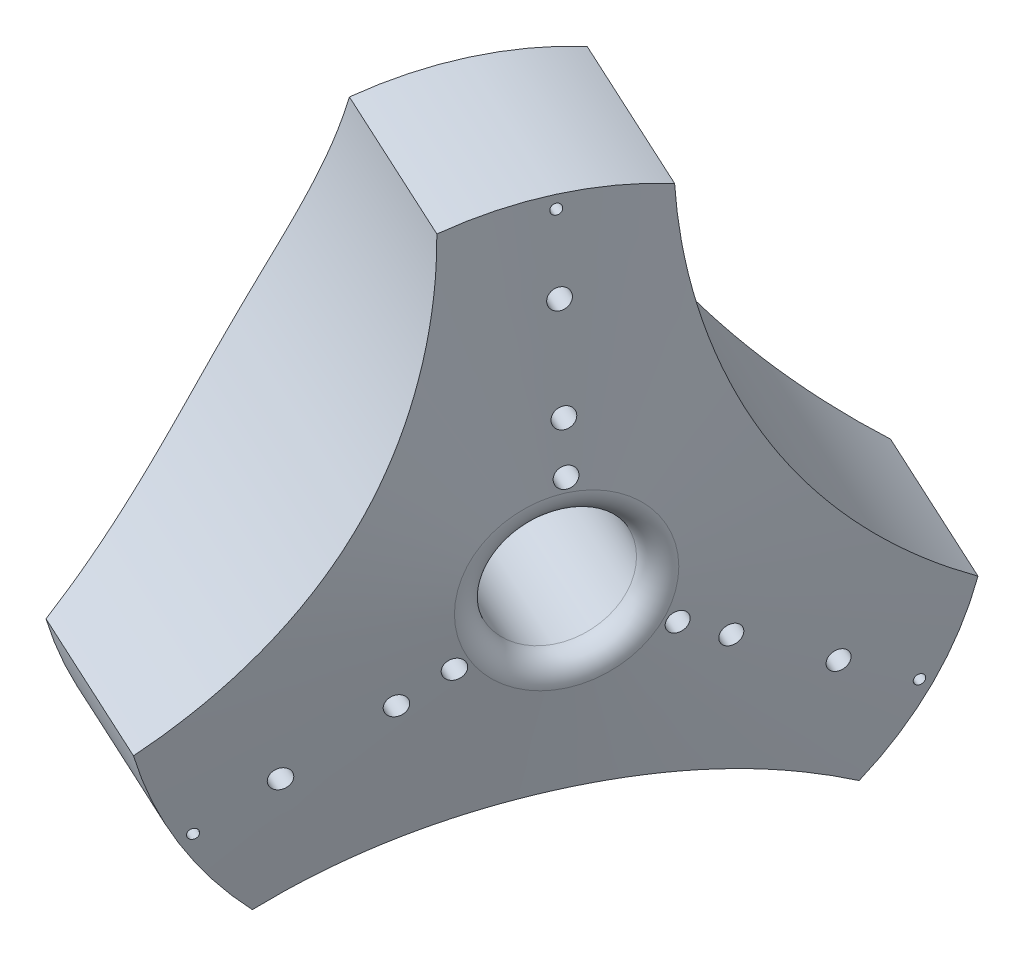
SolidWorks part; units mm, degrees
material "ABS"
ref_plane "前视基准面" through (0, 0, 0) normal (0, 0, 1) x (1, 0, 0)
ref_plane "上视基准面" through (0, 0, 0) normal (0, 1, 0) x (1, 0, 0)
ref_plane "右视基准面" through (0, 0, 0) normal (1, 0, 0) x (0, 0, -1)
other "Configuration Table"
sketch "草图1" plane through (0, 0, 0) normal (0, 1, 0) x (1, 0, 0)
  line L0 (0, 0) -> (50000, 0) construction
  line L1 (0, 0) -> (43301.2702, 25000) construction
  line L2 (0, 0) -> (24999.9996, 43301.2704) construction
  line L3 (0, 0) -> (0, 50000) construction
  line L4 (0, 0) -> (-25000, 43301.2702) construction
  line L5 (0, 0) -> (-43301.2704, 24999.9996) construction
  line L10 (33.4412, 57.9218) -> (0, 73.354)
  line L11 (0, 73.354) -> (0, 147.7852)
  line L12 (0, 147.7852) -> (67.3734, 116.6941)
  line L13 (18.3541, 0) -> (55.6014, 0)
  line L14 (-293.1662, 0) -> (-96.7748, 0)
  line L15 (67.3734, 116.6941) -> (33.4412, 57.9218)
  line L16 (36.9778, 130.7209) -> (32.7877, 121.641) construction
  line L17 (32.7877, 121.641) -> (62.3525, 107.9976)
  line L18 (32.7877, 121.641) -> (0, 136.7717)
  spline S0 degree 4 poles (0, -13.9122) (0.4288, -13.9878) (1.2926, -14.1039) (2.6002, -14.1722) (4.3419, -14.0551) (6.0103, -13.7444) (7.773, -13.21) (9.593, -12.4079) (11.2813, -11.3833) (13.0108, -9.9981) (14.579, -8.3636) (15.8921, -6.573) (16.7894, -4.9125) (17.3145, -3.6768) (17.5885, -2.9241) (17.7037, -2.5872) (17.8123, -2.2481) (17.9142, -1.9072) (18.0095, -1.5637) (18.0983, -1.2182) (18.1691, -0.9197) (18.2269, -0.6559) (18.2831, -0.3813) (18.3354, -0.109) (18.3711, 0.0925) (18.4139, 0.3573) (18.4465, 0.5746) (18.4705, 0.7447) (18.4976, 0.9523) (18.5267, 1.1986) (18.5568, 1.4891) (18.5855, 1.8227) (18.6082, 2.1561) (18.625, 2.4897) (18.6415, 2.9908) (18.6444, 3.7428) (18.6, 4.7901) (18.4544, 6.1268) (18.1183, 7.9493) (17.5241, 9.9881) (16.6153, 12.1533) (15.4328, 14.2054) (14.026, 16.1623) (12.2754, 18.1012) (10.149, 19.9482) (7.4457, 21.6944) (4.4784, 23.0742) (1.2971, 24.0486) (-2.1866, 24.6091) (-5.9175, 24.6633) (-9.7618, 24.1432) (-13.6227, 23.0043) (-17.2722, 21.3076) (-20.6387, 19.103) (-24.4169, 15.784) (-28.1648, 11.0227) (-31.3154, 4.4225) (-32.9538, -4.4321) (-32.0375, -14.0948) (-28.1424, -23.7302) (-21.3685, -32.1908) (-12.5515, -38.4704) (-2.4126, -42.2287) (8.3331, -43.3372) (19.0234, -41.8455) (29.7828, -37.6697) (40.3424, -30.2375) (49.4452, -19.1893) (55.5551, -4.7492) (57.3753, 11.4017) (54.7581, 27.4228) (48.0949, 42.2071) (37.9905, 54.8719) (25.1812, 64.7711) (10.4646, 71.4886) (-5.3559, 74.8179) (-21.5135, 74.7355) (-37.3086, 71.3698) (-52.1281, 64.9701) (-65.4574, 55.8769) (-76.8843, 44.4931) (-86.0992, 31.2617) (-92.9569, 16.4959) (-98.2612, -3.1071) (-99.3529, -27.5578) (-93.1302, -55.5464) (-77.0987, -83.8533) (-53.8578, -106.5556) (-25.4602, -122.2617) (5.9606, -130.2467) (38.3519, -130.3634) (69.8553, -122.9377) (98.8778, -108.6588) (124.1284, -88.4759) (144.6286, -63.5047) (159.7045, -34.9474) (168.9656, -4.026) (172.2746, 28.0696) (169.7138, 60.222) (161.5485, 91.4149) (148.1919, 120.752) (130.171, 147.4681) (108.095, 170.9338) (82.6276, 190.6548) (54.4619, 206.2675) (24.299, 217.5313) (-7.1689, 224.319) (-39.2739, 226.6058) (-71.3835, 224.4579) (-98.969, 218.8252) (-121.9134, 211.4493) (-140.4165, 203.6877) (-154.7919, 196.546) (-168.6874, 188.5108) (-182.0538, 179.6235) (-196.4446, 168.7156) (-208.5171, 158.129) (-219.9251, 146.8372) (-231.9749, 133.3951) (-241.9655, 120.8263) (-251.0758, 107.6061) (-258.3626, 95.6046) (-263.2354, 86.8412) (-266.9323, 79.7223) (-270.4259, 72.5015) (-273.7143, 65.185) (-276.4108, 58.7049) (-278.5921, 53.0984) (-280.3227, 48.3937) (-281.6549, 44.6108) (-282.9345, 40.8105) (-284.1616, 36.9917) (-285.3356, 33.1583) (-286.4574, 29.3057) (-287.5253, 25.4437) (-288.5419, 21.5581) (-289.5026, 17.675) (-290.3013, 14.2402) (-290.9454, 11.3302) (-291.4717, 8.8337) (-291.8579, 6.9561) (-292.2757, 4.8213) (-292.5987, 3.1456) (-293.0036, 0.9209) (-293.2168, -0.28) (-293.5445, -2.179) (-293.8363, -3.9367) (-294.1828, -6.1075) (-294.5484, -8.5333) (-294.8987, -10.9902) (-295.2261, -13.4346) (-295.5347, -15.89) (-295.8945, -18.9572) (-296.2863, -22.6451) (-296.6843, -26.9519) (-297.0589, -31.8818) (-297.3529, -36.8165) (-297.5669, -41.7558) (-297.7007, -46.6976) (-297.7547, -51.6411) (-297.729, -56.5848) (-297.624, -61.5274) (-297.4397, -66.4677) (-296.9135, -76.3411) (-295.6855, -89.8862) (-293.2164, -107.0261) (-288.82, -127.5848) (-284.8275, -141.8776) (-281.7816, -151.2859) (-280.1641, -155.9573) knots 0 0 0 0 0 0.000986 0.001973 0.002959 0.003945 0.004822 0.006138 0.007453 0.008403 0.009829 0.011255 0.012465 0.012667 0.012868 0.01307 0.013272 0.013473 0.013675 0.013876 0.014078 0.014179 0.01428 0.014481 0.01467 0.014765 0.01486 0.014954 0.015049 0.015238 0.015427 0.015617 0.015806 0.015995 0.016184 0.016752 0.017509 0.018368 0.019228 0.020946 0.022309 0.023673 0.024581 0.026398 0.028215 0.030031 0.031848 0.033788 0.035728 0.037999 0.04027 0.042541 0.044813 0.047084 0.049355 0.053897 0.05844 0.063467 0.069524 0.07558 0.081637 0.087693 0.093749 0.099806 0.105862 0.111919 0.119671 0.128756 0.137841 0.146925 0.15601 0.165095 0.174179 0.183264 0.192349 0.201434 0.210519 0.219603 0.228688 0.237773 0.246858 0.255942 0.265027 0.274475 0.292645 0.310814 0.328984 0.347153 0.365322 0.383492 0.401661 0.41983 0.438 0.456169 0.474339 0.492508 0.510678 0.528847 0.547017 0.565186 0.583356 0.601525 0.619695 0.637864 0.656034 0.674203 0.692373 0.710542 0.728712 0.746881 0.755966 0.765051 0.774136 0.78322 0.792305 0.80139 0.815017 0.81956 0.828644 0.842271 0.851356 0.855899 0.860441 0.864984 0.869526 0.874068 0.878611 0.880882 0.883153 0.885424 0.887695 0.889967 0.892238 0.894509 0.89678 0.899052 0.901323 0.903594 0.90473 0.905865 0.907001 0.908137 0.909272 0.910408 0.911108 0.911808 0.913208 0.914607 0.916007 0.917407 0.918807 0.920207 0.921607 0.924407 0.927206 0.930006 0.932806 0.935606 0.938405 0.941205 0.944005 0.946805 0.949604 0.952404 0.966403 0.977602 0.988801 1 1 1 1 1 construction
  spline S1 degree 4 poles (18.3541, 0) (18.3671, 0.0737) (18.3859, 0.1846) (18.4139, 0.3573) (18.4465, 0.5746) (18.4705, 0.7447) (18.4976, 0.9523) (18.5267, 1.1986) (18.5568, 1.4891) (18.5855, 1.8227) (18.6082, 2.1561) (18.625, 2.4897) (18.6415, 2.9908) (18.6444, 3.7428) (18.6, 4.7901) (18.4544, 6.1268) (18.1183, 7.9493) (17.5241, 9.9881) (16.6153, 12.1533) (15.4328, 14.2054) (14.026, 16.1623) (12.2754, 18.1012) (10.149, 19.9482) (7.4457, 21.6944) (4.4784, 23.0742) (1.2971, 24.0486) (-2.1866, 24.6091) (-5.9175, 24.6633) (-9.7618, 24.1432) (-13.6227, 23.0043) (-17.2722, 21.3076) (-20.6387, 19.103) (-24.4169, 15.784) (-28.1648, 11.0227) (-31.3154, 4.4225) (-32.9538, -4.4321) (-32.0375, -14.0948) (-28.1424, -23.7302) (-21.3685, -32.1908) (-12.5515, -38.4704) (-2.4126, -42.2287) (8.3331, -43.3372) (19.0234, -41.8455) (29.7828, -37.6697) (40.3424, -30.2375) (49.4452, -19.1893) (55.5551, -4.7492) (57.3753, 11.4017) (54.7581, 27.4228) (48.0949, 42.2071) (37.9905, 54.8719) (25.1812, 64.7711) (10.4646, 71.4886) (-5.3559, 74.8179) (-21.5135, 74.7355) (-37.3086, 71.3698) (-52.1281, 64.9701) (-65.4574, 55.8769) (-76.8843, 44.4931) (-86.0992, 31.2617) (-92.9569, 16.4959) (-98.2612, -3.1071) (-99.3529, -27.5578) (-93.1302, -55.5464) (-77.0987, -83.8533) (-53.8578, -106.5556) (-25.4602, -122.2617) (5.9606, -130.2467) (38.3519, -130.3634) (69.8553, -122.9377) (98.8778, -108.6588) (124.1284, -88.4759) (144.6286, -63.5047) (159.7045, -34.9474) (168.9656, -4.026) (172.2746, 28.0696) (169.7138, 60.222) (161.5485, 91.4149) (148.1919, 120.752) (130.171, 147.4681) (108.095, 170.9338) (82.6276, 190.6548) (54.4619, 206.2675) (24.299, 217.5313) (-7.1689, 224.319) (-39.2739, 226.6058) (-71.3835, 224.4579) (-98.969, 218.8252) (-121.9134, 211.4493) (-140.4165, 203.6877) (-154.7919, 196.546) (-168.6874, 188.5108) (-182.0538, 179.6235) (-196.4446, 168.7156) (-208.5171, 158.129) (-219.9251, 146.8372) (-231.9749, 133.3951) (-241.9655, 120.8263) (-251.0758, 107.6061) (-258.3626, 95.6046) (-263.2354, 86.8412) (-266.9323, 79.7223) (-270.4259, 72.5015) (-273.7143, 65.185) (-276.4108, 58.7049) (-278.5921, 53.0984) (-280.3227, 48.3937) (-281.6549, 44.6108) (-282.9345, 40.8105) (-284.1616, 36.9917) (-285.3356, 33.1583) (-286.4574, 29.3057) (-287.5253, 25.4437) (-288.5419, 21.5581) (-289.5026, 17.675) (-290.3013, 14.2402) (-290.9454, 11.3302) (-291.4717, 8.8337) (-291.8579, 6.9561) (-292.2757, 4.8213) (-292.5987, 3.1456) (-292.9346, 1.3001) (-293.0882, 0.4423) (-293.1662, 0) knots 0.014481 0.014481 0.014481 0.014481 0.014481 0.01467 0.014765 0.01486 0.014954 0.015049 0.015238 0.015427 0.015617 0.015806 0.015995 0.016184 0.016752 0.017509 0.018368 0.019228 0.020946 0.022309 0.023673 0.024581 0.026398 0.028215 0.030031 0.031848 0.033788 0.035728 0.037999 0.04027 0.042541 0.044813 0.047084 0.049355 0.053897 0.05844 0.063467 0.069524 0.07558 0.081637 0.087693 0.093749 0.099806 0.105862 0.111919 0.119671 0.128756 0.137841 0.146925 0.15601 0.165095 0.174179 0.183264 0.192349 0.201434 0.210519 0.219603 0.228688 0.237773 0.246858 0.255942 0.265027 0.274475 0.292645 0.310814 0.328984 0.347153 0.365322 0.383492 0.401661 0.41983 0.438 0.456169 0.474339 0.492508 0.510678 0.528847 0.547017 0.565186 0.583356 0.601525 0.619695 0.637864 0.656034 0.674203 0.692373 0.710542 0.728712 0.746881 0.755966 0.765051 0.774136 0.78322 0.792305 0.80139 0.815017 0.81956 0.828644 0.842271 0.851356 0.855899 0.860441 0.864984 0.869526 0.874068 0.878611 0.880882 0.883153 0.885424 0.887695 0.889967 0.892238 0.894509 0.89678 0.899052 0.901323 0.903594 0.90473 0.905865 0.907001 0.908137 0.909272 0.910408 0.910408 0.910408 0.910408 0.910408
  spline S2 degree 4 poles (18.4059, -25.3335) (19.107, -24.9916) (20.4868, -24.262) (22.5206, -23.0115) (25.0808, -21.0705) (27.4721, -18.8597) (29.6657, -16.3937) (31.6129, -13.729) (33.0896, -11.2475) (34.1864, -9.0304) (34.9057, -7.3212) (35.3416, -6.1645) (35.6757, -5.1903) (35.9253, -4.405) (36.1573, -3.6144) (36.3716, -2.8185) (36.5434, -2.119) (36.6687, -1.5643) (36.7535, -1.1663) (36.8052, -0.9135) (36.8466, -0.7052) (36.8982, -0.4372) (36.9567, -0.1213) (37.0035, 0.1434) (37.0749, 0.5721) (37.1371, 0.9717) (37.2058, 1.4486) (37.2819, 2.0322) (37.3587, 2.7131) (37.4305, 3.4924) (37.4863, 4.2735) (37.526, 5.0553) (37.5559, 6.0336) (37.5599, 7.208) (37.5186, 8.5778) (37.4086, 10.1401) (37.1505, 12.4751) (36.6019, 15.5617) (35.6708, 18.9675) (34.2579, 22.6243) (32.7042, 25.7897) (31.1185, 28.4933) (29.3394, 31.0737) (27.3788, 33.5189) (25.249, 35.8182) (22.9627, 37.9618) (20.5329, 39.9412) (17.3329, 42.201) (13.6843, 44.3112) (9.5794, 46.1791) (4.9351, 47.7364) (0.5493, 48.7741) (-5.1759, 49.5807) (-12.2448, 49.6897) (-20.4322, 48.5637) (-29.4144, 45.6531) (-37.7662, 41.2547) (-45.2725, 35.5359) (-51.7593, 28.6855) (-57.0931, 20.9063) (-61.1792, 12.4073) (-63.9591, 3.398) (-65.4072, -5.9168) (-65.5277, -15.3413) (-64.3508, -24.6913) (-61.9292, -33.7971) (-58.3342, -42.5053) (-53.6526, -50.6795) (-47.9834, -58.201) (-41.4348, -64.9693) (-34.1214, -70.9013) (-26.1617, -75.9314) (-17.6761, -80.0102) (-8.7848, -83.1042) (0.3937, -85.1942) (9.7443, -86.2746) (19.1561, -86.352) (28.5237, -85.4444) (37.7479, -83.5791) (48.7429, -80.1706) (61.3712, -74.3882) (74.9241, -65.3639) (88.2878, -52.3646) (99.2288, -36.9666) (107.3051, -19.8977) (112.3659, -1.711) (114.3597, 17.056) (113.3221, 35.8954) (109.3632, 54.3391) (102.6547, 71.9655) (93.418, 88.4046) (81.9129, 103.34) (68.427, 116.5097) (53.2659, 127.7056) (36.7454, 136.7708) (19.1839, 143.5977) (0.8963, 148.1237) (-17.8115, 150.3284) (-36.6464, 150.2287) (-55.332, 147.8751) (-73.6111, 143.3474) (-91.2474, 136.7503) (-108.0274, 128.21) (-121.7938, 119.1626) (-132.8352, 110.3812) (-141.486, 102.4316) (-148.0599, 95.7143) (-154.2723, 88.6613) (-160.1094, 81.2949) (-165.5592, 73.6375) (-171.8736, 63.7306) (-176.9453, 54.4461) (-180.9636, 45.947) (-183.8818, 38.8929) (-185.1615, 35.6104) (-186.1831, 32.858) (-186.9734, 30.6462) (-187.7366, 28.425) (-188.4727, 26.1945) (-189.1816, 23.9554) (-189.8633, 21.7077) (-190.5178, 19.4522) (-191.145, 17.1885) (-191.7448, 14.9181) (-192.3174, 12.6396) (-192.8623, 10.3561) (-193.3803, 8.0634) (-193.8088, 6.0566) (-194.131, 4.4692) (-194.3554, 3.3245) (-194.4957, 2.592) (-194.6042, 2.0172) (-194.7054, 1.4732) (-194.8177, 0.857) (-194.937, 0.1911) (-195.0219, -0.2913) (-195.1581, -1.0772) (-195.2723, -1.7539) (-195.4156, -2.6211) (-195.5862, -3.6835) (-195.7746, -4.9054) (-195.9819, -6.3152) (-196.2274, -8.0725) (-196.5025, -10.1875) (-196.7938, -12.6566) (-197.0869, -15.4841) (-197.3398, -18.3147) (-197.5528, -21.1491) (-197.7258, -23.9859) (-197.8589, -26.8251) (-197.9522, -29.6657) (-198.0191, -33.2178) (-198.0202, -37.4813) (-197.8411, -45.2961) (-197.0568, -56.6437) (-195.3598, -69.3345) (-193.0445, -80.4735) (-191.2905, -87.36) (-190.5403, -90.1013) knots 0 0 0 0 0 0.00302 0.006041 0.00923 0.01242 0.01561 0.0188 0.02199 0.023585 0.02518 0.025978 0.026776 0.027573 0.028371 0.029168 0.029966 0.030365 0.030564 0.030763 0.030963 0.031162 0.031561 0.03194 0.032319 0.032698 0.033077 0.033835 0.034592 0.03535 0.036108 0.036866 0.037624 0.039139 0.040655 0.042171 0.043686 0.048233 0.05278 0.055812 0.058843 0.061874 0.064906 0.067937 0.070969 0.074 0.077031 0.080063 0.086126 0.090292 0.094458 0.099005 0.103552 0.112646 0.12174 0.130835 0.139929 0.149023 0.158117 0.167211 0.176305 0.185399 0.194493 0.203588 0.212682 0.221776 0.23087 0.239964 0.249059 0.258153 0.267247 0.276341 0.285435 0.294529 0.303624 0.312718 0.321812 0.330906 0.34 0.349094 0.36631 0.384498 0.402687 0.420875 0.439063 0.457252 0.47544 0.493628 0.511817 0.530005 0.548193 0.566382 0.58457 0.602758 0.620947 0.639135 0.657323 0.675512 0.6937 0.711888 0.730077 0.748265 0.766453 0.784642 0.793736 0.80283 0.811924 0.821018 0.830112 0.839207 0.848301 0.866489 0.871036 0.875583 0.877857 0.88013 0.882404 0.884678 0.886951 0.889225 0.891498 0.893772 0.896045 0.898319 0.900592 0.902866 0.90514 0.907413 0.90855 0.909118 0.909687 0.910255 0.910823 0.911392 0.91196 0.912648 0.913336 0.914024 0.914711 0.916087 0.917463 0.918838 0.920214 0.922965 0.925716 0.928468 0.931219 0.93397 0.936721 0.939473 0.942224 0.944975 0.950478 0.95598 0.972488 0.988995 1 1 1 1 1 construction
  spline S3 degree 4 poles (36.9778, 0) (36.9927, 0.0848) (37.022, 0.2547) (37.0749, 0.5721) (37.1371, 0.9717) (37.2058, 1.4486) (37.2819, 2.0322) (37.3587, 2.7131) (37.4305, 3.4924) (37.4863, 4.2735) (37.526, 5.0553) (37.5559, 6.0336) (37.5599, 7.208) (37.5186, 8.5778) (37.4086, 10.1401) (37.1505, 12.4751) (36.6019, 15.5617) (35.6708, 18.9675) (34.2579, 22.6243) (32.7042, 25.7897) (31.1185, 28.4933) (29.3394, 31.0737) (27.3788, 33.5189) (25.249, 35.8182) (22.9627, 37.9618) (20.5329, 39.9412) (17.3329, 42.201) (13.6843, 44.3112) (9.5794, 46.1791) (4.9351, 47.7364) (0.5493, 48.7741) (-5.1759, 49.5807) (-12.2448, 49.6897) (-20.4322, 48.5637) (-29.4144, 45.6531) (-37.7662, 41.2547) (-45.2725, 35.5359) (-51.7593, 28.6855) (-57.0931, 20.9063) (-61.1792, 12.4073) (-63.9591, 3.398) (-65.4072, -5.9168) (-65.5277, -15.3413) (-64.3508, -24.6913) (-61.9292, -33.7971) (-58.3342, -42.5053) (-53.6526, -50.6795) (-47.9834, -58.201) (-41.4348, -64.9693) (-34.1214, -70.9013) (-26.1617, -75.9314) (-17.6761, -80.0102) (-8.7848, -83.1042) (0.3937, -85.1942) (9.7443, -86.2746) (19.1561, -86.352) (28.5237, -85.4444) (37.7479, -83.5791) (48.7429, -80.1706) (61.3712, -74.3882) (74.9241, -65.3639) (88.2878, -52.3646) (99.2288, -36.9666) (107.3051, -19.8977) (112.3659, -1.711) (114.3597, 17.056) (113.3221, 35.8954) (109.3632, 54.3391) (102.6547, 71.9655) (93.418, 88.4046) (81.9129, 103.34) (68.427, 116.5097) (53.2659, 127.7056) (36.7454, 136.7708) (19.1839, 143.5977) (0.8963, 148.1237) (-17.8115, 150.3284) (-36.6464, 150.2287) (-55.332, 147.8751) (-73.6111, 143.3474) (-91.2474, 136.7503) (-108.0274, 128.21) (-121.7938, 119.1626) (-132.8352, 110.3812) (-141.486, 102.4316) (-148.0599, 95.7143) (-154.2723, 88.6613) (-160.1094, 81.2949) (-165.5592, 73.6375) (-171.8736, 63.7306) (-176.9453, 54.4461) (-180.9636, 45.947) (-183.8818, 38.8929) (-185.1615, 35.6104) (-186.1831, 32.858) (-186.9734, 30.6462) (-187.7366, 28.425) (-188.4727, 26.1945) (-189.1816, 23.9554) (-189.8633, 21.7077) (-190.5178, 19.4522) (-191.145, 17.1885) (-191.7448, 14.9181) (-192.3174, 12.6396) (-192.8623, 10.3561) (-193.3803, 8.0634) (-193.8088, 6.0566) (-194.131, 4.4692) (-194.3554, 3.3245) (-194.4957, 2.592) (-194.6042, 2.0172) (-194.7054, 1.4732) (-194.8177, 0.857) (-194.9027, 0.3825) (-194.948, 0.1273) (-194.9705, 0) knots 0.031561 0.031561 0.031561 0.031561 0.031561 0.03194 0.032319 0.032698 0.033077 0.033835 0.034592 0.03535 0.036108 0.036866 0.037624 0.039139 0.040655 0.042171 0.043686 0.048233 0.05278 0.055812 0.058843 0.061874 0.064906 0.067937 0.070969 0.074 0.077031 0.080063 0.086126 0.090292 0.094458 0.099005 0.103552 0.112646 0.12174 0.130835 0.139929 0.149023 0.158117 0.167211 0.176305 0.185399 0.194493 0.203588 0.212682 0.221776 0.23087 0.239964 0.249059 0.258153 0.267247 0.276341 0.285435 0.294529 0.303624 0.312718 0.321812 0.330906 0.34 0.349094 0.36631 0.384498 0.402687 0.420875 0.439063 0.457252 0.47544 0.493628 0.511817 0.530005 0.548193 0.566382 0.58457 0.602758 0.620947 0.639135 0.657323 0.675512 0.6937 0.711888 0.730077 0.748265 0.766453 0.784642 0.793736 0.80283 0.811924 0.821018 0.830112 0.839207 0.848301 0.866489 0.871036 0.875583 0.877857 0.88013 0.882404 0.884678 0.886951 0.889225 0.891498 0.893772 0.896045 0.898319 0.900592 0.902866 0.90514 0.907413 0.90855 0.909118 0.909687 0.910255 0.910823 0.911392 0.91196 0.91196 0.91196 0.91196 0.91196
  dimension "D1" = 10
revolve "旋转1" add sketch "草图1" angle 360 about L12 region at (24.8259, 0, -97.4748) region at (17.1802, 0, -66.4951)
ref_plane "基准面1" through (10.3172, 0, 4.7611) normal (0.908, 0, 0.419) x (0.419, 0, -0.908)
sketch "草图2" plane through (10.3172, 0, 4.7611) normal (0.908, 0, 0.419) x (0.419, 0, -0.908)
  line L0 (134.1862, 0) -> (134.1862, 20) construction
  line L1 (134.1862, 20) -> (134.1862, 30) construction
  line L2 (134.1862, 30) -> (134.1862, 50) construction
  line L3 (134.1862, 67.5821) -> (134.1862, 65.0821)
  line L4 (134.1862, 0) -> (17.2728, 67.5) construction
  circle A0 centre (134.1862, 0) radius 67.5821 construction
  circle A1 centre (134.1862, 65.0821) radius 1
  circle A2 centre (134.1862, 50) radius 2
  circle A3 centre (134.1862, 30) radius 2
  circle A4 centre (134.1862, 20) radius 2
  circle A5 centre (17.2728, 67.5) radius 98.5
  circle A6 centre (251.0996, 67.5) radius 98.5
  circle A7 centre (190.5489, -32.541) radius 1
  circle A8 centre (177.4875, -25) radius 2
  circle A9 centre (160.1669, -15) radius 2
  circle A10 centre (151.5067, -10) radius 2
  circle A11 centre (134.1862, -135) radius 98.5
  circle A12 centre (77.8234, -32.541) radius 1
  circle A13 centre (90.8849, -25) radius 2
  circle A14 centre (108.2054, -15) radius 2
  circle A15 centre (116.8657, -10) radius 2
  circle A16 centre (134.1862, 0) radius 12.5
  dimension "D5" = 2
  dimension "D6" = 4
  dimension "D7" = 4
  dimension "D8" = 4
  dimension "D10" = 197
  dimension "D12" = 25
  dimension "D1" = 20
  dimension "D2" = 10
  dimension "D3" = 20
  dimension "D4" = 2.5
  dimension "D9" = 60
  dimension "D11" = 3
extrude "切除-拉伸1" cut sketch "草图2" against normal blind 103 contours A5 | A6 | A11 | A10 | A9 | A16 | A8 | A7 | A15 | A14 | A13 | A12 | A4 | A3 | A2 | A1 region at (17.5546, 67.5, -10.9222) region at (115.5305, 67.5, -223.2327) region at (77.4288, -15, -140.6675) region at (73.8, -10, -132.8042) region at (66.5426, -135, -117.0775) region at (66.5426, 0, -117.0775)
fillet "圆角1" radius 4.5 1 edges at (61.0972, 0, -105.8235)
shell "抽壳1" thickness 2
ref_plane "基准面2" through (55.3874, 0, -120.0226) normal (0.419, 0, -0.908) x (-0.908, 0, -0.419)
ref_plane "基准面3" through (56.2254, 0, -121.8386) normal (0.419, 0, -0.908) x (-0.908, 0, -0.419)
sketch "草图3" plane through (56.2254, 0, -121.8386) normal (0.419, 0, -0.908) x (-0.908, 0, -0.419)
  line L0 (-9.2549, 16.4959) -> (52.5587, 16.4959)
  line L1 (-8.2736, 26.3749) -> (49.2409, 26.3749)
  line L2 (-8.2736, 26.3749) -> (-8.2736, 23.3681)
  line L3 (-8.2736, 23.3681) -> (49.2409, 23.3681)
  line L4 (49.2409, 26.3749) -> (49.2409, 23.3681)
  line L5 (52.5587, 16.4959) -> (53.6991, 14.0836)
  line L6 (53.6991, 14.0836) -> (-9.2549, 14.0836)
  line L7 (-9.2549, 14.0836) -> (-9.2549, 16.4959)
  line L8 (-5.7909, 53.7259) -> (35.2465, 53.7259)
  line L9 (35.2465, 53.7259) -> (31.1223, 62.4502)
  line L10 (31.1223, 62.4502) -> (-5.0562, 62.4502)
  line L11 (-5.0562, 62.4502) -> (-5.7909, 53.7259)
extrude "凸台-拉伸1" add sketch "草图3" along normal mid plane 1
ref_axis "基准轴1" through (-3.3985, 0, -149.3535) along (0.908, 0, 0.419)
pattern_circular "阵列(圆周)1" count 3 over 360 about axis through (-3.3985, 0, -149.3535) along (0.908, 0, 0.419) of "凸台-拉伸1"
